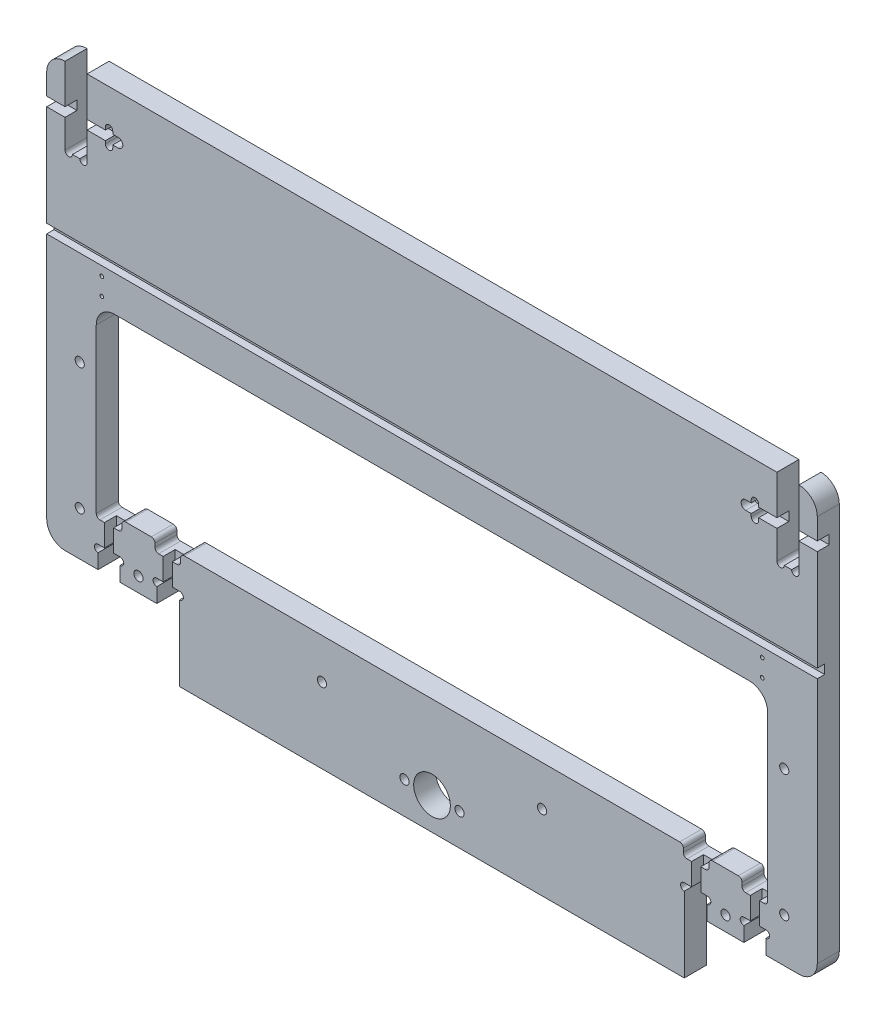
SolidWorks part; units mm, degrees
other "DetailItem1"
other "DetailItem2"
material "HDPE-green"
ref_plane "Front Plane" through (0, 0, 0) normal (0, 0, 1) x (1, 0, 0)
ref_plane "Top Plane" through (0, 0, 0) normal (0, 1, 0) x (1, 0, 0)
ref_plane "Right Plane" through (0, 0, 0) normal (1, 0, 0) x (0, 0, -1)
sketch "Sketch1" plane through (0, 0, 0) normal (0, 0, 1) x (1, 0, 0)
  line L1 (-137.5, -16.5) -> (137.5, -16.5)
  line L2 (-137.5, -16.5) -> (-137.5, 16.5)
  line L3 (-137.5, 16.5) -> (137.5, 16.5)
  line L4 (137.5, -16.5) -> (137.5, 16.5)
  line L5 (-137.5, -16.5) -> (137.5, 16.5) construction
  line L6 (-137.5, 16.5) -> (137.5, -16.5) construction
  point P0 (0, 0)
  dimension "D1" = 275
  dimension "D2" = 33
extrude "Boss-Extrude1" add sketch "Sketch1" along normal blind 12
sketch "Sketch2" plane through (0, 0, 12) normal (0, 0, 1) x (1, 0, 0)
  line L0 (137.5, 16.5) -> (-137.5, 16.5) construction
  line L1 (-15, 1) -> (21.5379, 1) construction
  circle A0 centre (0, 1) radius 10
  circle A1 centre (-15, 1) radius 2.5
  circle A2 centre (15, 1) radius 2.5
  point P2 (0, 16.5)
  dimension "D1" = 15.5
  dimension "D2" = 20
  dimension "D3" = 5
  dimension "D4" = 5
  dimension "D5" = 30
  dimension "D6" = 15
extrude "Cut-Extrude1" cut sketch "Sketch2" against normal up to next
sketch "Sketch3" plane through (0, 0, 12) normal (0, 0, 1) x (1, 0, 0)
  line L0 (-137.5, -16.5) -> (137.5, -16.5) construction
  line L1 (-210, 16.5) -> (210, 16.5)
  line L2 (-210, 16.5) -> (-210, 46.5)
  line L3 (-183, 46.5) -> (183, 46.5)
  line L4 (210, 16.5) -> (210, 46.5)
  line L5 (-183, 141.5) -> (183, 141.5)
  line L6 (-210, 46.5) -> (-210, 247.5)
  line L7 (-210, 247.5) -> (210, 247.5)
  line L8 (-183, 46.5) -> (-183, 141.5)
  line L11 (210, 46.5) -> (210, 247.5)
  line L13 (183, 46.5) -> (183, 141.5)
  circle A0 centre (0, 1) radius 10 construction
  dimension "D1" = 30
  dimension "D2" = 420
  dimension "D3" = 210
  dimension "D5" = 264
  dimension "D8" = 95
extrude "Boss-Extrude2" add sketch "Sketch3" against normal blind 12
sketch "Sketch5" plane through (0, 0, 12) normal (0, 0, 1) x (1, 0, 0)
  line L0 (-183, 46.5) -> (-183, 40.5)
  line L1 (-183, 40.5) -> (-169, 40.5)
  line L2 (-169, 40.5) -> (-169, 46.5)
  line L3 (183, 46.5) -> (-183, 46.5) construction
  line L4 (-169, 46.5) -> (-183, 46.5)
  line L5 (-151, 46.5) -> (-151, 40.5)
  line L6 (-151, 40.5) -> (-137, 40.5)
  line L7 (-137, 40.5) -> (-137, 46.5)
  line L8 (-151, 46.5) -> (-137, 46.5)
  circle A0 centre (0, 1) radius 10 construction
  dimension "D1" = 14
  dimension "D2" = 6
  dimension "D3" = 6
  dimension "D4" = 14
  dimension "D5" = 137
  dimension "D6" = 169
extrude "Cut-Extrude3" cut sketch "Sketch5" against normal up to next
fillet "Fillet1" radius 2 7 edges at (-137, 40.5, 6) (-151, 40.5, 6) (-169, 40.5, 6) (-183, 40.5, 6) (-137, 46.5, 6) (-169, 46.5, 6) (-151, 46.5, 6)
mirror "Mirror2" about plane through (0, 0, 0) normal (1, 0, 0) of "Fillet1", "Cut-Extrude3"
sketch "Sketch8" plane through (0, 0, 12) normal (0, 0, 1) x (1, 0, 0)
  line L0 (0, 79.2288) -> (0, 236.3795) construction
  line L1 (210, 247.5) -> (-210, 247.5) construction
  line L2 (-188, 247.5) -> (-200, 247.5)
  line L3 (-188, 247.5) -> (-188, 205.5)
  line L4 (-188, 205.5) -> (-200, 205.5)
  line L5 (-200, 247.5) -> (-200, 205.5)
  line L7 (188, 247.5) -> (200, 247.5)
  line L8 (188, 247.5) -> (188, 205.5)
  line L9 (188, 205.5) -> (200, 205.5)
  line L10 (200, 247.5) -> (200, 205.5)
  dimension "D1" = 376
  dimension "D2" = 188
  dimension "D3" = 12
  dimension "D4" = 12
  dimension "D5" = 42
  dimension "D6" = 42
extrude "Cut-Extrude6" cut sketch "Sketch8" against normal up to next
hole_wizard "Ø5.0 (5) Diameter Hole2" positions "Sketch10" profile "Sketch9" hole size "Ø5.0" standard "ISO" end condition up to next
sketch "Sketch10" plane through (0, 0, 0) normal (0, 0, -1) x (-1, 0, 0)
  line L0 (183, 141.5) -> (183, 42.5) construction
  line L1 (210, 16.5) -> (137.5, 16.5) construction
  point P0 (192, 109.5)
  point P1 (192, 40.5)
  dimension "D1" = 9
  dimension "D2" = 9
  dimension "D3" = 93
  dimension "D4" = 24
sketch "Sketch9" plane through (-192, 109.5, 0) normal (1, 0, 0) x (0, 1, 0)
  line L0 (0, 0) -> (0, 12.001)
  line L1 (0, 12.001) -> (2.5, 12.001)
  line L2 (2.5, 12.001) -> (2.5, 0)
  line L5 (2.5, 0) -> (0, 0)
  line L11 (0, -6.35) -> (0, 107.95) construction
  dimension "Thru Hole Dia." = 5
  dimension "Thru Hole Depth" = 12.001
mirror "Mirror3" about plane through (0, 0, 0) normal (1, 0, 0) of "Ø5.0 (5) Diameter Hole2"
sketch "Sketch23" plane through (0, 0, 12) normal (0, 0, 1) x (1, 0, 0)
  line L0 (-194.5668, 223.5) -> (-160.7966, 223.5) construction
  line L1 (188, 247.5) -> (-188, 247.5) construction
  line L2 (-176, 219.5) -> (-176, 227.5) construction
  line L3 (-178, 219.5) -> (-178, 227.5)
  line L4 (-174, 219.5) -> (-174, 227.5)
  line L5 (-188, 205.5) -> (-188, 247.5) construction
  arc A0 (-178, 219.5) -> (-174, 219.5) centre (-176, 219.5) ccw
  arc A1 (-174, 227.5) -> (-178, 227.5) centre (-176, 227.5) ccw
  point P6 (-176, 223.5)
  dimension "D2" = 2
  dimension "D1" = 24
  dimension "D3" = 8
  dimension "D4" = 12
extrude "Cut-Extrude9" cut sketch "Sketch23" against normal blind 8
sketch "Sketch24" plane through (0, 0, 12) normal (0, 0, 1) x (1, 0, 0)
  line L0 (-189.7724, 223.5) -> (-168.9128, 223.5) construction
  line L1 (-222.7334, 223.5) -> (-171, 223.5) construction
  line L2 (-222.7334, 226) -> (-171, 226)
  line L3 (-222.7334, 221) -> (-171, 221)
  line L4 (-188, 205.5) -> (-188, 247.5) construction
  arc A0 (-222.7334, 226) -> (-222.7334, 221) centre (-222.7334, 223.5) ccw
  arc A1 (-171, 221) -> (-171, 226) centre (-171, 223.5) ccw
  point P4 (-196.8667, 223.5)
  dimension "D1" = 2.5
  dimension "D2" = 17
extrude "Cut-Extrude10" cut sketch "Sketch24" against normal blind 6.5
hole_wizard "Ø5.0 (5) Diameter Hole1" positions "Sketch18" profile "Sketch17" hole size "Ø5.0" standard "ISO" end condition up to next
sketch "Sketch18" plane through (0, 0, 0) normal (0, 0, -1) x (-1, 0, 0)
  line L0 (137.5, -16.5) -> (-137.5, -16.5) construction
  line L3 (137.5, -16.5) -> (-137.5, -16.5) construction
  circle A0 centre (0, 1) radius 10 construction
  circle A1 centre (0, 1) radius 10 construction
  point P1 (-60, 24.5)
  point P3 (60, 24.5)
  point P16 (160, 24.5)
  point P18 (-160, 24.5)
  dimension "D2" = 41
  dimension "D3" = 41
  dimension "D4" = 41
  dimension "D5" = 41
  dimension "D7" = 60
  dimension "D8" = 60
  dimension "D9" = 160
  dimension "D10" = 160
sketch "Sketch17" plane through (60, 24.5, 0) normal (1, 0, 0) x (0, 1, 0)
  line L0 (0, 0) -> (0, 12)
  line L1 (0, 12) -> (2.5, 12)
  line L2 (2.5, 12) -> (2.5, 0)
  line L5 (2.5, 0) -> (0, 0)
  line L11 (0, -6.35) -> (0, 107.95) construction
  dimension "Thru Hole Dia." = 5
  dimension "Thru Hole Depth" = 12
hole_wizard "Ø2.0 (2) Diameter Hole1" positions "Sketch20" profile "Sketch19" hole size "Ø2.0" standard "ISO" end condition up to next
sketch "Sketch20" plane through (0, 0, 12) normal (0, 0, 1) x (1, 0, 0)
  line L0 (183, 141.5) -> (-183, 141.5) construction
  line L1 (-188, 205.5) -> (-188, 221) construction
  point P0 (-180, 156)
  point P1 (-180, 146.5)
  dimension "D1" = 9.5
  dimension "D2" = 5
  dimension "D3" = 8
  dimension "D4" = 8
sketch "Sketch19" plane through (-180, 156, 12) normal (1, 0, 0) x (0, -1, 0)
  line L0 (0, 0) -> (0, 12.0011)
  line L1 (0, 12.0011) -> (1, 12.0011)
  line L2 (1, 12.0011) -> (1, 0)
  line L5 (1, 0) -> (0, 0)
  line L11 (0, -6.35) -> (0, 107.95) construction
  dimension "Thru Hole Dia." = 2
  dimension "Thru Hole Depth" = 12.0011
mirror "Mirror4" about plane through (0, 0, 0) normal (1, 0, 0) of "Cut-Extrude10", "Ø2.0 (2) Diameter Hole1", "Cut-Extrude9"
sketch "Sketch21" plane through (0, 0, 12) normal (0, 0, 1) x (1, 0, 0)
  line L1 (-213.7408, 161) -> (233.06, 161)
  line L2 (-213.7408, 161) -> (-213.7408, 166)
  line L3 (-213.7408, 166) -> (233.06, 166)
  line L4 (233.06, 161) -> (233.06, 166)
  line L5 (-213.7408, 161) -> (233.06, 166) construction
  line L6 (-213.7408, 166) -> (233.06, 161) construction
  circle A0 centre (-180, 156) radius 1 construction
  point P0 (9.6596, 163.5)
  dimension "D1" = 5
  dimension "D2" = 5
extrude "Cut-Extrude7" cut sketch "Sketch21" against normal blind 4
fillet "Fillet2" radius 10 6 edges at (210, 247.5, 6) (210, 16.5, 6) (-210, 16.5, 6) (-210, 247.5, 6) (183, 141.5, 6) (-183, 141.5, 6)
sketch "Sketch25" plane through (0, 0, 12) normal (0, 0, 1) x (1, 0, 0)
  line L0 (-181, 40.5) -> (-171, 40.5) construction
  line L1 (-178.5, 52.5) -> (-173.5, 52.5)
  line L2 (-178.5, 52.5) -> (-178.5, 28.5)
  line L3 (-178.5, 28.5) -> (-173.5, 28.5)
  line L4 (-173.5, 52.5) -> (-173.5, 28.5)
  line L5 (-178.5, 52.5) -> (-173.5, 28.5) construction
  line L6 (-178.5, 28.5) -> (-173.5, 52.5) construction
  line L7 (-149, 40.5) -> (-139, 40.5) construction
  line L8 (-146.5, 52.5) -> (-141.5, 52.5)
  line L9 (-146.5, 52.5) -> (-146.5, 28.5)
  line L10 (-146.5, 28.5) -> (-141.5, 28.5)
  line L11 (-141.5, 52.5) -> (-141.5, 28.5)
  line L12 (-146.5, 52.5) -> (-141.5, 28.5) construction
  line L13 (-146.5, 28.5) -> (-141.5, 52.5) construction
  point P0 (-176, 40.5)
  point P7 (-144, 40.5)
  dimension "D1" = 5
  dimension "D2" = 5
  dimension "D3" = 24
  dimension "D4" = 24
extrude "Cut-Extrude11" cut sketch "Sketch25" against normal blind 6.5
sketch "Sketch26" plane through (0, 0, 12) normal (0, 0, 1) x (1, 0, 0)
  line L0 (-200, 16.5) -> (-137.5, 16.5) construction
  line L1 (-182, 16.5) -> (-170, 16.5)
  line L2 (-182, 16.5) -> (-182, 24.5)
  line L3 (-182, 28.5) -> (-170, 28.5)
  line L4 (-170, 16.5) -> (-170, 24.5)
  line L5 (-181, 40.5) -> (-171, 40.5) construction
  line L6 (-150, 16.5) -> (-137.5, 16.5)
  line L7 (-150, 16.5) -> (-150, 24.5)
  line L8 (-150, 28.5) -> (-137.5, 28.5)
  line L9 (-137.5, 16.5) -> (-137.5, 24.5)
  line L10 (-149, 40.5) -> (-139, 40.5) construction
  arc A0 (-182, 28.5) -> (-182, 24.5) centre (-182, 26.5) ccw
  arc A1 (-170, 24.5) -> (-170, 28.5) centre (-170, 26.5) ccw
  arc A2 (-150, 28.5) -> (-150, 24.5) centre (-150, 26.5) ccw
  arc A3 (-137.5, 24.5) -> (-137.5, 28.5) centre (-137.5, 26.5) ccw
  point P10 (-176, 40.5)
  point P13 (-144, 40.5)
  dimension "D7" = 4
  dimension "D8" = 4
  dimension "D9" = 4
  dimension "D10" = 4
  dimension "D1" = 12
  dimension "D2" = 12
  dimension "D3" = 12
  dimension "D4" = 12.5
  dimension "D5" = 6
  dimension "D6" = 6
extrude "Cut-Extrude12" cut sketch "Sketch26" against normal up to next
mirror "Mirror5" about plane through (0, 0, 0) normal (1, 0, 0) of "Cut-Extrude12", "Cut-Extrude11"
sketch "Sketch27" plane through (0, 0, 12) normal (0, 0, 1) x (1, 0, 0)
  line L0 (-200, 205.5) -> (-188, 205.5) construction
  line L1 (188, 205.5) -> (200, 205.5) construction
  circle A0 centre (-198, 205.5) radius 2
  circle A1 centre (-190, 205.5) radius 2
  circle A2 centre (190, 205.5) radius 2
  circle A3 centre (198, 205.5) radius 2
  dimension "D1" = 4
  dimension "D2" = 4
  dimension "D3" = 4
  dimension "D4" = 4
extrude "Cut-Extrude13" cut sketch "Sketch27" against normal up to next
